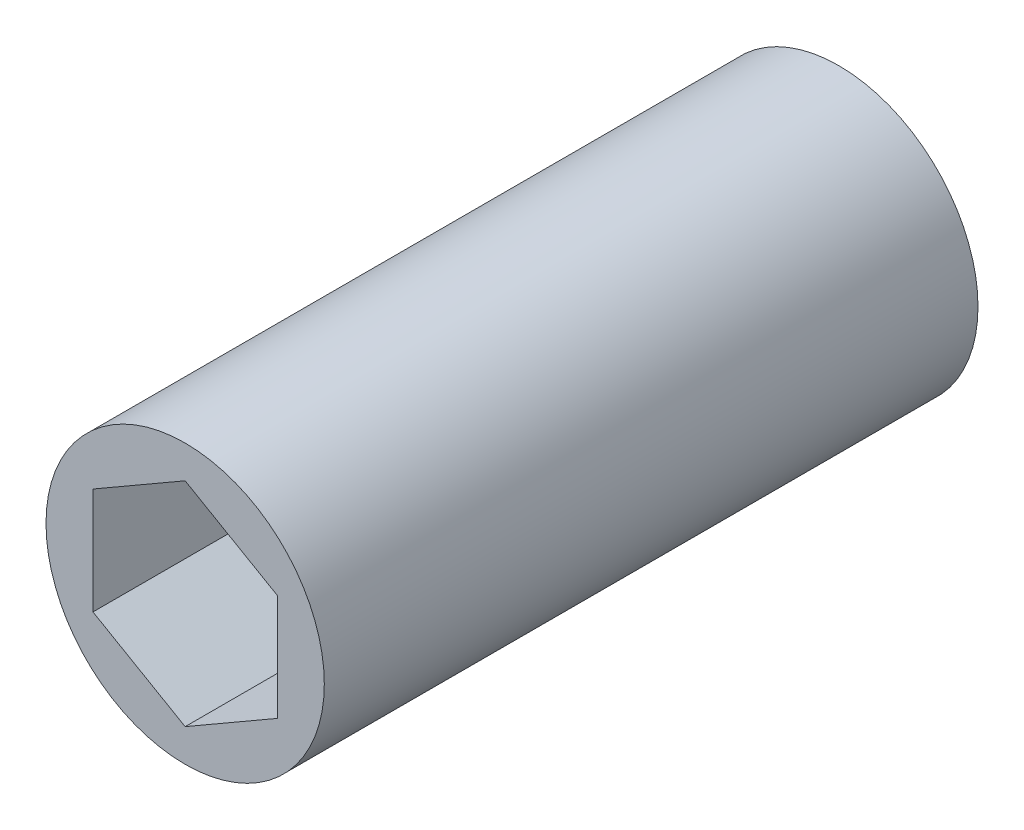
SolidWorks part; units mm, degrees
material "Nylon 101"
ref_plane "Front Plane" through (0, 0, 0) normal (0, 0, 1) x (1, 0, 0)
ref_plane "Top Plane" through (0, 0, 0) normal (0, 1, 0) x (1, 0, 0)
ref_plane "Right Plane" through (0, 0, 0) normal (1, 0, 0) x (0, 0, -1)
sketch "Sketch1" plane through (0, 0, 0) normal (0, 0, 1) x (1, 0, 0)
  line L1 (0, 7.7723) -> (-6.731, 3.8861)
  line L2 (-6.731, 3.8861) -> (-6.731, -3.8861)
  line L3 (-6.731, -3.8861) -> (0, -7.7723)
  line L4 (0, -7.7723) -> (6.731, -3.8861)
  line L5 (6.731, -3.8861) -> (6.731, 3.8861)
  line L6 (6.731, 3.8861) -> (0, 7.7723)
  circle A0 centre (0, 0) radius 10.16
  circle A1 centre (0, 0) radius 6.731 construction
  point P3 (0, 0)
  dimension "D1" = 13.462
  dimension "D2" = 20.32
extrude "Boss-Extrude1" add sketch "Sketch1" along normal mid plane 47.7266
